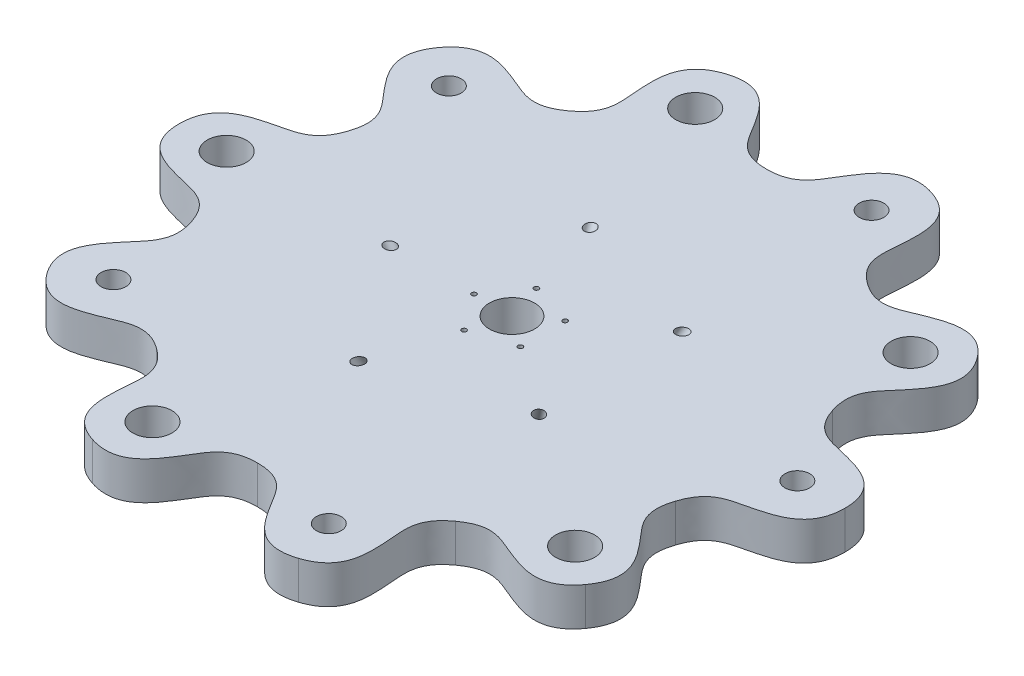
SolidWorks part; units mm, degrees
note: The reader was unsure of these and kept them because the rebuilt part matched: shared geometry of "Sketch19<3>", "Sketch19<8>".
other "Markup1"
sketch "Sketch22" plane through (67.4, 16.5, 67.4) normal (0.6133, 0.6241, 0.4841) x (0.6587, -0.0661, -0.7495)
sketch "Sketch37" plane through (67.4, 28, 67.4) normal (0.6133, 0.6241, 0.4841) x (0.6587, -0.0661, -0.7495)
other "Markup2"
sketch "Sketch23" plane through (67.4, 26.5, 67.4) normal (0.1362, 0.0894, 0.9866) x (0.9893, -0.0646, -0.1307)
sketch "Sketch38" plane through (67.4, 28, 67.4) normal (0.1362, 0.0894, 0.9866) x (0.9893, -0.0646, -0.1307)
other "Markup5"
sketch "Sketch28" plane through (-67.4, 30.5, 67.4) normal (-0.0176, 0.5562, 0.8308) x (0.9998, 0.0146, 0.0115)
sketch "Sketch39" plane through (-67.4, 28, 67.4) normal (-0.0176, 0.5562, 0.8308) x (0.9998, 0.0146, 0.0115)
material "1023 Carbon Steel Sheet (SS)"
ref_plane "Front Plane" through (0, 0, 0) normal (0, 0, 1) x (1, 0, 0)
ref_plane "Top Plane" through (0, 0, 0) normal (0, 1, 0) x (1, 0, 0)
ref_plane "Right Plane" through (0, 0, 0) normal (1, 0, 0) x (0, 0, -1)
sketch "Sketch1" plane through (0, 0, 0) normal (0, 0, 1) x (1, 0, 0)
  line L5 (-47.4, 0) -> (-47.4, -8)
  line L9 (-7, -8) -> (0, -8)
  line L10 (0, -8) -> (0, 0)
  line L12 (-7, -8) -> (-17.4, -8)
  line L24 (-17.4, -8) -> (-47.4, -8)
  line L25 (-47.4, 0) -> (0, 0)
  dimension "D2" = 8
  dimension "D3" = 47.4
  dimension "D8" = 0
  dimension "D10" = 7
revolve "Revolve1" add sketch "Sketch1" angle 360 about L10
sketch "Sketch4" plane through (0, 0, 0) normal (0, 0, 1) x (1, 0, 0)
  line L0 (0, 0) -> (0, 13.3666) construction
sketch "Sketch2" plane through (0, 0, 0) normal (0, 1, 0) x (1, 0, 0)
  circle A0 centre (-8, 0) radius 0.5
  dimension "D2" = 1
  dimension "D1" = 8
extrude "Fuel holes" cut sketch "Sketch2" against normal up to next from offset 5
pattern_circular "CirPattern1" count 5 over 360 about axis through (0, 0, 0) along (0, 1, 0) of "Fuel holes" reverse direction yes
sketch "Sketch5" plane through (0, 0, 0) normal (1, 0, 0) x (0, 0, -1)
sketch "Sketch19" plane through (0, -8, 0) normal (0, -1, 0) x (1, 0, 0)
  line L0 (-47.4, 0) -> (-70, 0) construction
  line L1 (-56.6312, -41.145) -> (0, 0) construction
  line L4 (0, 0) -> (-66.574, -21.6312) construction
  line L5 (-51.8483, -13.5569) -> (-50.8815, -16.5324) construction
  line L9 (-69, 0) -> (-70, 0)
  line L11 (-53.7996, 39.0877) -> (-54.2257, 38.5013)
  circle A1 centre (0, 0) radius 47.4
  circle A2 centre (0, 0) radius 70 construction
  circle A3 centre (-60, 0) radius 4.1
  circle A4 centre (0, 0) radius 47.4 construction
  circle A5 centre (-48.541, -35.2671) radius 2.6
  circle A6 centre (0, 0) radius 53.5
  circle A8 centre (0, 0) radius 70
  spline S0 degree 3 poles (-50.8815, -16.5324) (-52.4491, -11.7078) (-59.9998, -9.5551) (-70, -7.7496) (-70, 0) knots 0 0 0 0 0.376166 1 1 1 1
  spline S1 degree 3 poles (-50.8815, -16.5324) (-49.3139, -21.357) (-54.1572, -27.5367) (-61.1863, -34.8754) (-56.6312, -41.145) knots 0 0 0 0 0.376166 1 1 1 1
  dimension "D2" = 8.2
  dimension "D5" = 5.2
  dimension "D7" = 107
  dimension "D3" = 60
  dimension "D4" = 36
  dimension "D6" = 60
  dimension "D8" = 18
  dimension "D1" = 22.6
extrude "Boss-Extrude2" add sketch "Sketch19" against normal blind 8
extrude "Bolt holes" cut sketch "Sketch19<3>" against normal up to surface (8 mm away) contours A3 | A5
sketch "Sketch19<3>" plane through (0, -8, 0) normal (0, -1, 0) x (1, 0, 0) same geometry as "Sketch19"
extrude "Grooves" cut sketch "Sketch19<8>" against normal through all contours S1 S0 A8
sketch "Sketch19<8>" plane through (0, -8, 0) normal (0, -1, 0) x (1, 0, 0) same geometry as "Sketch19"
sketch "Sketch21" plane through (0, 0, 0) normal (0, 0, 1) x (1, 0, 0)
  line L0 (0, 0) -> (51.8972, 0) construction
  line L1 (0, 0) -> (0, -5.4672) construction
sketch "Sketch8" plane through (-29.8564, -8, 0) normal (0, -1, 0) x (-1, 0, 0)
  line L0 (-29.8564, 0) -> (-8.8564, 0) construction
  line L1 (-8.8564, 0) -> (-8.8564, 32.0516) construction
  circle A2 centre (-8.8564, 0) radius 1.75
  dimension "D1" = 3.5
  dimension "D2" = 21
ref_plane "Plane1" through (-21, 0, 0) normal (1, 0, 0) x (0, 0, -1)
ref_plane "Plane2" through (-1.7859, 3.0933, 0) normal (0.5, -0.866, 0) x (0, 0, -1)
sketch "Sketch41" plane through (-1.7859, 3.0933, 0) normal (0.5, -0.866, 0) x (0, 0, -1)
  circle A0 centre (0, -22.1865) radius 1.15
  dimension "D1" = 2.3
extrude "Cut-Extrude7" cut sketch "Sketch41" against normal blind 10 and the other way through all
sketch "Sketch31" plane through (0, -8, 0) normal (0, -1, 0) x (1, 0, 0)
  circle A0 centre (0, 0) radius 27.4
  dimension "D1" = 54.8
sketch "Sketch32" plane through (0, 0, 0) normal (0, 1, 0) x (1, 0, 0)
  circle A0 centre (0, 0) radius 5.5 construction
  circle A1 centre (0, 0) radius 4.75
  dimension "M11_threads" = 11
  dimension "M11Tap" = 9.5
sketch "Sketch35" plane through (0, 0, 0) normal (0, 0, 1) x (1, 0, 0)
  line L0 (0, 0) -> (0, 22.3821) construction
pattern_circular "CirPattern9" count 5 over 360 about axis through (0, 0, 0) along (0, 1, 0) of "Cut-Extrude7"
pattern_circular "CirPattern10" count 5 over 360 about axis through (0, 0, 0) along (0, 1, 0) of "Bolt holes"
pattern_circular "CirPattern11" count 10 over 360 about axis through (0, 0, 0) along (0, 1, 0) of "Grooves"
extrude "M11Tap" cut sketch "Sketch32" against normal through all contours A1
cosmetic thread "Cosmetic Thread1" parameters "D2"=11
equation "\"Bolts\"= 10"
equation "\"D4@Sketch19\"=360/\"Bolts\""
equation "\"D7@Sketch19\"=102+2.5*2"
equation "\"D8@Sketch19\"=\"D4@Sketch19\"/2"
